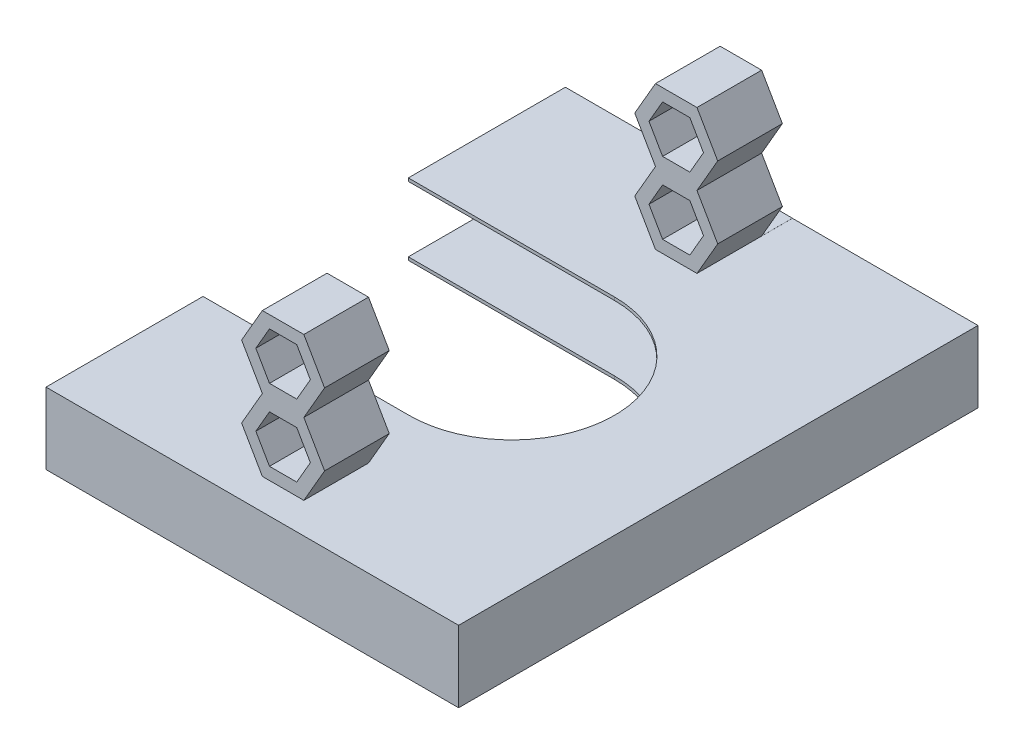
SolidWorks part; units mm, degrees
ref_plane "Front Plane" through (0, 0, 0) normal (0, 0, 1) x (1, 0, 0)
ref_plane "Top Plane" through (0, 0, 0) normal (0, 1, 0) x (1, 0, 0)
ref_plane "Right Plane" through (0, 0, 0) normal (1, 0, 0) x (0, 0, -1)
sketch "Sketch2" plane through (0, 0, 0) normal (0, 0, 1) x (1, 0, 0)
  line L0 (3.0311, 2.5013) -> (4.0415, 2.5013)
  line L1 (4.0415, 4.2513) -> (3.0311, 6.0013)
  line L2 (0, 0) -> (4.0415, 0)
  line L3 (0, 0) -> (0, 2.5013)
  line L4 (0, 2.5013) -> (1.0104, 2.5013)
  line L5 (4.0415, 0) -> (4.0415, 2.5013)
  line L7 (1.0104, 6.0013) -> (0, 4.2513)
  line L8 (0, 4.2513) -> (1.0104, 2.5013)
  line L10 (3.0311, 2.5013) -> (4.0415, 4.2513)
  line L11 (4.0415, 7.7513) -> (3.0311, 9.5013)
  line L12 (3.0311, 9.5013) -> (1.0104, 9.5013)
  line L13 (1.0104, 9.5013) -> (0, 7.7513)
  line L14 (0, 7.7513) -> (1.0104, 6.0013)
  line L16 (3.0311, 6.0013) -> (4.0415, 7.7513)
  line L17 (2.0207, 6.0013) -> (3.0311, 6.0013) [skipped]
  line L18 (3.0311, 6.0013) -> (2.0207, 6.0013) [skipped]
  line L19 (2.0207, 2.5013) -> (3.0311, 2.5013) [skipped]
  circle A0 centre (2.0207, 4.2513) radius 1.75 construction
  circle A1 centre (2.0207, 7.7513) radius 1.75 construction
extrude "Boss-Extrude1" add sketch "Sketch2" along normal blind 25.3 contours L1 L16 L11 L12 L13 L14 L7 L8 L4 L3 L2 L5 L0 L10
sketch "Sketch3" plane through (0, 0, 25.3) normal (0, 0, 1) x (1, 0, 0)
  line L0 (1.0104, 9.5013) -> (0, 7.7513) construction
  line L1 (3.3486, 7.7513) -> (2.6847, 8.9013)
  line L2 (2.6847, 8.9013) -> (1.3568, 8.9013)
  line L3 (1.3568, 8.9013) -> (0.6928, 7.7513)
  line L4 (0.6928, 7.7513) -> (1.3568, 6.6013)
  line L5 (1.3568, 6.6013) -> (2.6847, 6.6013)
  line L6 (2.6847, 6.6013) -> (3.3486, 7.7513)
  line L7 (3.0311, 6.0013) -> (4.0415, 7.7513) construction
  line L8 (4.0415, 7.7513) -> (3.0311, 9.5013) construction
  line L11 (3.3486, 4.2513) -> (2.6847, 5.4013)
  line L12 (2.6847, 5.4013) -> (1.3568, 5.4013)
  line L13 (1.3568, 5.4013) -> (0.6928, 4.2513)
  line L14 (0.6928, 4.2513) -> (1.3568, 3.1013)
  line L15 (1.3568, 3.1013) -> (2.6847, 3.1013)
  line L16 (2.6847, 3.1013) -> (3.3486, 4.2513)
  line L17 (1.0104, 6.0013) -> (0, 4.2513) construction
  line L18 (0, 4.2513) -> (1.0104, 2.5013) construction
  line L19 (4.0415, 4.2513) -> (3.0311, 6.0013) construction
  circle A0 centre (2.0207, 7.7513) radius 1.15 construction
  circle A1 centre (2.0207, 4.2513) radius 1.15 construction
  dimension "D1" = 0.6
  dimension "D2" = 0.6
  dimension "D3" = 0.6
  dimension "D4" = 0.6
  dimension "D5" = 0.6
  dimension "D6" = 0.6
extrude "Cut-Extrude1" cut sketch "Sketch3" against normal blind 25.3
sketch "Sketch14" plane through (0, 0, 0) normal (0, 0, -1) x (-1, 0, 0)
  line L1 (-4.2364, 9.6861) -> (0.2393, 9.6861)
  line L2 (-4.2364, 9.6861) -> (-4.2364, 2.5073)
  line L3 (-4.2364, 2.5073) -> (0.2393, 2.5073)
  line L4 (0.2393, 9.6861) -> (0.2393, 2.5073)
extrude "Cut-Extrude6" cut sketch "Sketch14" against normal blind 1.5
sketch "Sketch15" plane through (0, 0, 25.3) normal (0, 0, 1) x (1, 0, 0)
  line L1 (0, 9.6086) -> (4.0415, 9.6086)
  line L2 (0, 9.6086) -> (0, 2.5013)
  line L3 (0, 2.5013) -> (4.0415, 2.5013)
  line L4 (4.0415, 9.6086) -> (4.0415, 2.5013)
extrude "Cut-Extrude7" cut sketch "Sketch15" against normal blind 1.5
sketch "Sketch16" plane through (0, 9.5013, 0) normal (0, 1, 0) x (1, 0, 0)
  line L1 (-0.7522, -4.65) -> (4.5577, -4.65)
  line L2 (-0.7522, -4.65) -> (-0.7522, -20.65)
  line L3 (-0.7522, -20.65) -> (4.5577, -20.65)
  line L4 (4.5577, -4.65) -> (4.5577, -20.65)
  line L6 (1.0104, -1.5) -> (3.0311, -1.5) construction
  line L7 (3.0311, -23.8) -> (1.0104, -23.8) construction
  point P4 (1.9027, -4.65)
  dimension "D1" = 16
  dimension "D2" = 3.15
  dimension "D3" = 3.15
extrude "Cut-Extrude8" cut sketch "Sketch16" against normal blind 7
sketch "Sketch17" plane through (4.0415, 0, 0) normal (1, 0, 0) x (0, 0, -1)
  line L1 (-25.3, 2.5013) -> (0, 2.5013)
  line L2 (-25.3, 2.5013) -> (-25.3, 0)
  line L3 (-25.3, 0) -> (0, 0)
  line L4 (0, 2.5013) -> (0, 0)
extrude "Boss-Extrude2" add sketch "Sketch17" along normal blind 8.0293
sketch "Sketch18" plane through (0, 0, 0) normal (-1, 0, 0) x (0, 0, 1)
  line L1 (0, 0) -> (25.3, 0)
  line L2 (0, 0) -> (0, 2.5013)
  line L3 (0, 2.5013) -> (25.3, 2.5013)
  line L4 (25.3, 0) -> (25.3, 2.5013)
extrude "Boss-Extrude3" add sketch "Sketch18" along normal blind 8.0293
sketch "Sketch20" plane through (0, 0, 0) normal (0, -1, 0) x (1, 0, 0)
  line L1 (-8.0293, 0) -> (12.0707, 0)
  line L2 (-8.0293, 0) -> (-8.0293, 25.3)
  line L3 (-8.0293, 25.3) -> (12.0707, 25.3)
  line L4 (12.0707, 0) -> (12.0707, 25.3)
extrude "Boss-Extrude4" add sketch "Sketch20" along normal blind 0.9787
sketch "Sketch21" plane through (0, 2.5013, 0) normal (0, 1, 0) x (1, 0, 0)
  line L2 (-8.0293, -25.3) -> (-8.0293, 0) construction
  line L3 (-8.0293, -7.65) -> (2.0107, -7.65)
  line L4 (-8.0293, -7.65) -> (-8.0293, -17.65)
  line L5 (-8.0293, -17.65) -> (2.0107, -17.65)
  arc A0 (2.0107, -17.65) -> (2.0107, -7.65) centre (2.0107, -12.65) ccw
  point P1 (-25.4578, -7.2891)
extrude "Cut-Extrude9" cut sketch "Sketch21" against normal blind 3.48 contours A0 L3 L4 L5
sketch "Sketch22" plane through (-8.0293, 0, 0) normal (-1, 0, 0) x (0, 0, 1)
  line L0 (7.65, 2.5013) -> (0, 2.5013) construction
  line L1 (0.15, -0.8287) -> (25.15, -0.8287)
  line L2 (0.15, -0.8287) -> (0.15, 2.3513)
  line L3 (0.15, 2.3513) -> (25.15, 2.3513)
  line L4 (25.15, -0.8287) -> (25.15, 2.3513)
  line L5 (0, 2.5013) -> (0, -0.9787) construction
  dimension "D1" = 25
  dimension "D2" = 3.18
  dimension "D3" = 0.15
  dimension "D4" = 0.15
extrude "Cut-Extrude10" cut sketch "Sketch22" against normal blind 19.8
